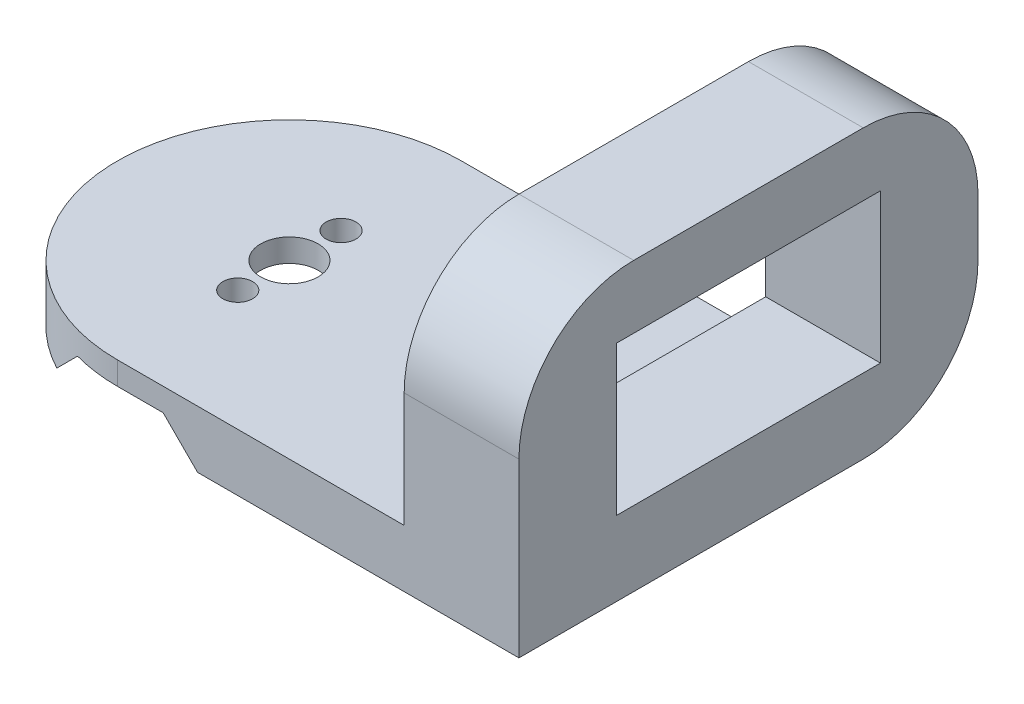
SolidWorks part; units mm, degrees
ref_plane "Front Plane" through (0, 0, 0) normal (0, 0, 1) x (1, 0, 0)
ref_plane "Top Plane" through (0, 0, 0) normal (0, 1, 0) x (1, 0, 0)
ref_plane "Right Plane" through (0, 0, 0) normal (1, 0, 0) x (0, 0, -1)
sketch "Sketch1" plane through (0, 0, 0) normal (0, 1, 0) x (1, 0, 0)
  line L0 (0, 0) -> (25, 0) construction
  line L1 (0, 15) -> (25, 15)
  line L2 (0, -15) -> (25, -15)
  line L3 (25, 15) -> (25, -15)
  arc A0 (0, 15) -> (0, -15) centre (0, 0) ccw
  circle A2 centre (0, 0) radius 2.5
  circle A3 centre (0, -4.5) radius 1.3
  circle A4 centre (0, 4.5) radius 1.3
  point P3 (31.1712, 0)
  dimension "D1" = 15
  dimension "D3" = 5
  dimension "D4" = 2.6
  dimension "D5" = 2.6
  dimension "D2" = 25
  dimension "D6" = 9
extrude "Boss-Extrude1" add sketch "Sketch1" along normal blind 5
sketch "Sketch2" plane through (25, 0, 0) normal (1, 0, 0) x (0, 0, -1)
  line L1 (-15, 0) -> (25, 0)
  line L2 (-15, 0) -> (-15, 25)
  line L3 (-15, 25) -> (25, 25)
  line L4 (25, 0) -> (25, 25)
  dimension "D1" = 25
  dimension "D2" = 40
extrude "Boss-Extrude2" add sketch "Sketch2" along normal blind 10
sketch "Sketch3" plane through (25, 0, 0) normal (1, 0, 0) x (0, 0, -1)
  line L0 (-15, 0) -> (25, 0) construction
  line L2 (-6.5, 19.5) -> (16.5, 19.5)
  line L3 (-6.5, 19.5) -> (-6.5, 6.5)
  line L4 (-6.5, 6.5) -> (16.5, 6.5)
  line L5 (16.5, 19.5) -> (16.5, 6.5)
  circle A0 centre (0, 13) radius 6.5
  circle A1 centre (-9, 13) radius 1.05
  circle A2 centre (19, 13) radius 1.05
  dimension "D2" = 13
  dimension "D6" = 2.1
  dimension "D1" = 13
  dimension "D3" = 23
  dimension "D4" = 9
  dimension "D5" = 19
extrude "Cut-Extrude1" cut sketch "Sketch3" along normal blind 8 contours L2 L5 L4 L3
extrude "Cut-Extrude2" cut sketch "Sketch3<3>" along normal blind 8 contours A1 | A2
sketch "Sketch3<3>" plane through (25, 0, 0) normal (1, 0, 0) x (0, 0, -1) same geometry as "Sketch3"
extrude "Cut-Extrude3" cut sketch "Sketch3<4>" along normal through all contours L2 L5 L4 L3
sketch "Sketch3<4>" plane through (25, 0, 0) normal (1, 0, 0) x (0, 0, -1) same geometry as "Sketch3"
fillet "Fillet1" radius 10 3 edges at (30, 0, -25) (30, 25, -25) (30, 25, 15)
fillet "Fillet3" [suppressed] radius 3
sketch "Sketch4" plane through (0, 0, 15) normal (0, 0, 1) x (1, 0, 0)
  line L0 (7, 0) -> (4, 3)
  line L1 (0, 0) -> (35, 0) construction
  line L2 (4, 3) -> (-4, 3)
  line L3 (-4, 3) -> (-7, 0)
  line L4 (-15, 0) -> (0, 0) construction
  line L5 (-7, 0) -> (7, 0)
  point P4 (0, 0)
  dimension "D1" = 3
  dimension "D2" = 45
  dimension "D3" = 8
extrude "Cut-Extrude4" cut sketch "Sketch4" against normal through all
